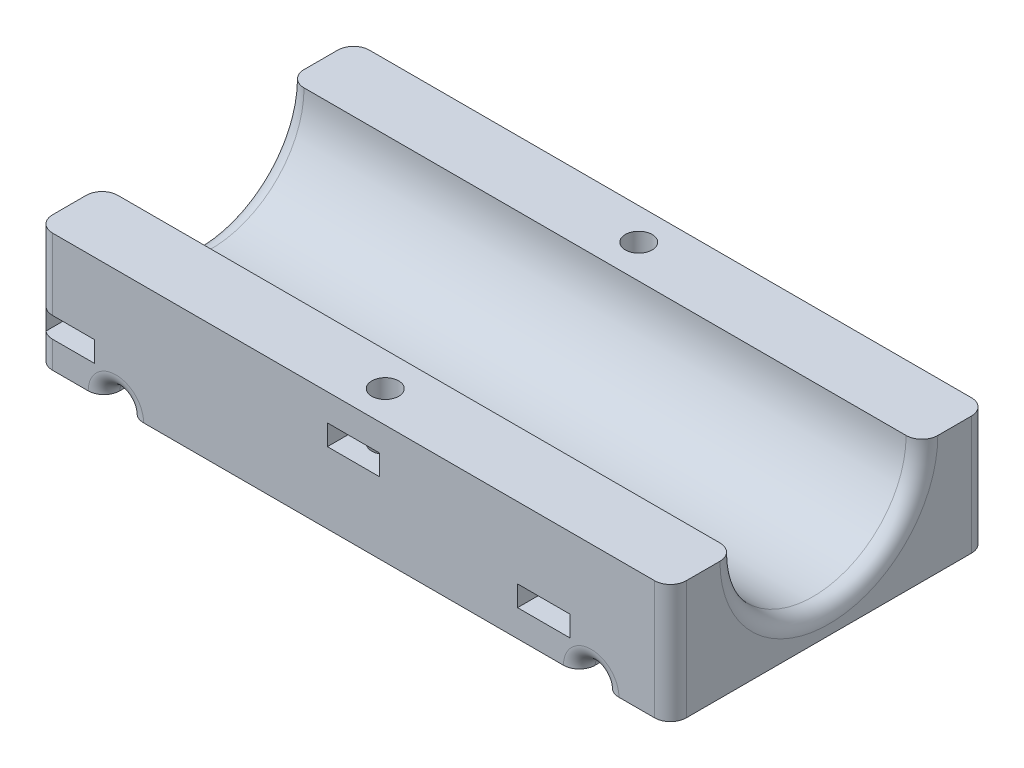
SolidWorks part; units mm, degrees
ref_plane "Front Plane" through (0, 0, 0) normal (0, 0, 1) x (1, 0, 0)
ref_plane "Top Plane" through (0, 0, 0) normal (0, 1, 0) x (1, 0, 0)
ref_plane "Right Plane" through (0, 0, 0) normal (1, 0, 0) x (0, 0, -1)
sketch "Sketch3" plane through (0, 0, 0) normal (1, 0, 0) x (0, 0, -1)
  line L0 (40.3225, 19.05) -> (50.8, 19.05)
  line L1 (0, 0) -> (50.8, 0)
  line L2 (0, 0) -> (0, 19.05)
  line L3 (0, 19.05) -> (10.4775, 19.05)
  line L4 (50.8, 0) -> (50.8, 19.05)
  arc A0 (10.4775, 19.05) -> (40.3225, 19.05) centre (25.4, 19.05) ccw
  point P9 (25.4, 0)
  dimension "D1" = 14.9225
  dimension "D2" = 50.8
  dimension "D3" = 19.05
extrude "Boss-Extrude2" add sketch "Sketch3" along normal blind 101.6
sketch "Sketch4" plane through (0, 0, 0) normal (0, 0, 1) x (1, 0, 0)
  line L0 (101.6, 0) -> (0, 0) construction
  line L1 (0, 19.05) -> (0, 0) construction
  circle A0 centre (12.7, 0) radius 1.905
  circle A1 centre (88.9, 0) radius 1.905
  dimension "D1" = 3.81
  dimension "D2" = 76.2
  dimension "D3" = 12.7
extrude "Cut-Extrude1" cut sketch "Sketch4" against normal through all
hole_wizard "#6 Clearance Hole1" positions "Sketch5" profile "Sketch6" hole size "#6" standard "ANSI Inch"
sketch "Sketch5" plane through (0, 19.05, 0) normal (0, 1, 0) x (1, 0, 0)
  line L0 (101.6, 0) -> (0, 0) construction
  line L1 (0, 25.4) -> (101.6, 25.4) construction
  line L2 (0, 40.3225) -> (0, 10.4775) construction
  line L3 (101.6, 10.4775) -> (101.6, 40.3225) construction
  line L4 (50.8, 0) -> (50.8, 50.8) construction
  line L5 (101.6, 50.8) -> (0, 50.8) construction
  point P0 (50.8, 5.08)
  point P2 (50.8, 45.72)
  point P29 (0, 0)
  point P30 (0, 0)
  dimension "D1" = 5.08
sketch "Sketch6" plane through (50.8, 19.05, -5.08) normal (1, 0, 0) x (0, 0, 1)
  line L0 (0, 0) -> (0, 13.9934)
  line L1 (0, 13.9934) -> (2.1526, 12.7)
  line L2 (2.1526, 12.7) -> (2.1526, 0)
  line L5 (2.1526, 0) -> (0, 0)
  line L10 (0, 13.9934) -> (-2.1527, 12.7) construction
  line L11 (0, -6.35) -> (0, 107.95) construction
  dimension "Hole Dia." = 4.3053
  dimension "Hole Depth" = 12.7
  dimension "Drill Angle" = 118
ref_plane "Plane1" through (0, 11.43, 0) normal (0, 1, 0) x (1, 0, 0)
sketch "Sketch8" plane through (0, 11.43, 0) normal (0, 1, 0) x (1, 0, 0)
  line L0 (101.6, 0) -> (0, 0) construction
  line L1 (46.609, 9.144) -> (54.991, 9.144)
  line L2 (46.609, 9.144) -> (46.609, 0)
  line L3 (46.609, 0) -> (54.991, 0)
  line L4 (54.991, 9.144) -> (54.991, 0)
  line L5 (101.6, 50.8) -> (0, 50.8) construction
  line L6 (46.609, 41.656) -> (54.991, 41.656)
  line L7 (46.609, 41.656) -> (46.609, 50.8)
  line L8 (46.609, 50.8) -> (54.991, 50.8)
  line L9 (54.991, 41.656) -> (54.991, 50.8)
  point P12 (50.8, 9.144)
  dimension "D1" = 8.382
  dimension "D2" = 4.064
extrude "Cut-Extrude2" cut sketch "Sketch8" along normal blind 3.302
hole_wizard "#6 Clearance Hole2" positions "Sketch9" profile "Sketch10" hole size "#6" standard "ANSI Inch"
sketch "Sketch9" plane through (0, 0, 0) normal (0, -1, 0) x (-1, 0, 0)
  line L0 (-101.6, 0) -> (-101.6, 50.8) construction
  line L1 (-101.6, 50.8) -> (-90.805, 50.8) construction
  line L2 (0, 0) -> (0, 50.8) construction
  point P0 (-96.52, 45.72)
  point P2 (-81.28, 5.6113)
  point P4 (-20.32, 45.72)
  point P6 (-5.08, 5.6113)
  point P16 (0, 0)
  point P17 (0, 0)
  dimension "D1" = 5.08
  dimension "D2" = 5.08
  dimension "D3" = 5.08
  dimension "D4" = 15.24
  dimension "D5" = 15.24
sketch "Sketch10" plane through (96.52, 0, -45.72) normal (1, 0, 0) x (0, 0, -1)
  line L0 (0, 0) -> (0, 13.9934)
  line L1 (0, 13.9934) -> (2.1526, 12.7)
  line L2 (2.1526, 12.7) -> (2.1526, 0)
  line L5 (2.1526, 0) -> (0, 0)
  line L10 (0, 13.9934) -> (-2.1527, 12.7) construction
  line L11 (0, -6.35) -> (0, 107.95) construction
  dimension "Hole Dia." = 4.3053
  dimension "Hole Depth" = 12.7
  dimension "Drill Angle" = 118
ref_plane "Plane2" through (0, 7.62, 0) normal (0, -1, 0) x (-1, 0, 0)
sketch "Sketch11" plane through (0, 7.62, 0) normal (0, -1, 0) x (-1, 0, 0)
  line L0 (-101.6, 50.8) -> (-90.805, 50.8) construction
  line L1 (-100.711, 41.656) -> (-92.329, 41.656)
  line L2 (-100.711, 41.656) -> (-100.711, 50.8)
  line L3 (-100.711, 50.8) -> (-92.329, 50.8)
  line L4 (-92.329, 41.656) -> (-92.329, 50.8)
  line L5 (-86.995, 50.8) -> (-14.605, 50.8) construction
  line L6 (-24.511, 41.656) -> (-16.129, 41.656)
  line L7 (-24.511, 41.656) -> (-24.511, 50.8)
  line L8 (-24.511, 50.8) -> (-16.129, 50.8)
  line L9 (-16.129, 41.656) -> (-16.129, 50.8)
  line L10 (-86.995, 0) -> (-14.605, 0) construction
  line L11 (-85.471, 0) -> (-77.089, 0)
  line L12 (-85.471, 0) -> (-85.471, 9.144)
  line L13 (-85.471, 9.144) -> (-77.089, 9.144)
  line L14 (-77.089, 0) -> (-77.089, 9.144)
  line L15 (-10.795, 0) -> (0, 0) construction
  line L16 (-9.271, 9.144) -> (-0.889, 9.144)
  line L17 (-9.271, 9.144) -> (-9.271, 0)
  line L18 (-9.271, 0) -> (-0.889, 0)
  line L19 (-0.889, 9.144) -> (-0.889, 0)
  point P24 (-96.52, 41.656)
  point P25 (-81.28, 9.144)
  point P26 (-20.32, 41.656)
  point P29 (-5.08, 9.144)
  point P30 (-9.271, 12.6166)
  point P33 (-77.089, 10.6597)
  dimension "D1" = 8.382
  dimension "D2" = 4.064
extrude "Cut-Extrude3" cut sketch "Sketch11" along normal blind 3.302
fillet "Fillet1" radius 2.54 10 edges at (101.6, 4.1275, -25.4) (0, 4.1275, -25.4) (0, 9.525, -50.8) (101.6, 9.525, -50.8) (0, 9.525, 0) (101.6, 9.525, 0) (88.9, 1.905, -50.8) (88.9, 1.905, 0) (12.7, 1.905, -50.8) (12.7, 1.905, 0)
